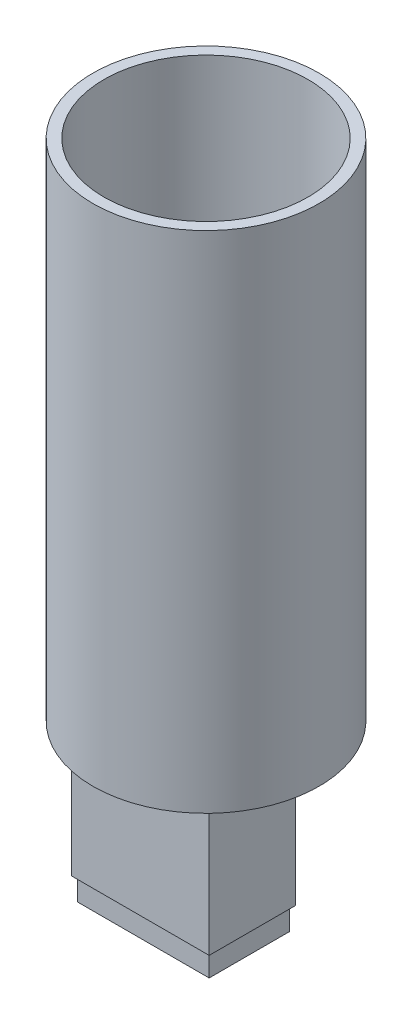
SolidWorks part; units mm, degrees
ref_plane "Front Plane" through (0, 0, 0) normal (0, 0, 1) x (1, 0, 0)
ref_plane "Top Plane" through (0, 0, 0) normal (0, 1, 0) x (1, 0, 0)
ref_plane "Right Plane" through (0, 0, 0) normal (1, 0, 0) x (0, 0, -1)
sketch "Sketch1" plane through (0, 0, 0) normal (0, 1, 0) x (1, 0, 0)
  circle A1 centre (0, 0) radius 15.01
  dimension "D2" = 30.02
extrude "Boss-Extrude1" add sketch "Sketch1" along normal blind 67 contours A1
sketch "Sketch2" plane through (0, 67, 0) normal (0, 1, 0) x (1, 0, 0)
  circle A0 centre (0, 0) radius 13.54
  dimension "D1" = 27.08
extrude "Cut-Extrude1" cut sketch "Sketch2" against normal blind 65
sketch "Sketch3" plane through (0, 0, 0) normal (0, -1, 0) x (1, 0, 0)
  line L1 (-9.15, 8.73) -> (9.15, 8.73)
  line L2 (-9.15, 8.73) -> (-9.15, -2.71)
  line L3 (-9.15, -2.71) -> (9.15, -2.71)
  line L4 (9.15, 8.73) -> (9.15, -2.71)
  line L5 (-9.15, 8.73) -> (9.15, -2.71) construction
  line L6 (-9.15, -2.71) -> (9.15, 8.73) construction
  circle A0 centre (0, 0) radius 15.01 construction
  point P0 (0, 3.01)
  dimension "D1" = 11.44
  dimension "D2" = 18.3
  dimension "D3" = 3.01
extrude "Boss-Extrude2" add sketch "Sketch3" along normal blind 18
ref_plane "Plane1" through (0, 0, 0) normal (0, -1, 0) x (-1, 0, 0)
sketch "Sketch4" plane through (0, 0, 0) normal (0, -1, 0) x (-1, 0, 0)
  line L0 (9.15, 2.71) -> (-9.15, 2.71) construction
  line L1 (-7.65, 1.21) -> (7.65, 1.21)
  line L2 (-7.65, 1.21) -> (-7.65, -7.23)
  line L3 (-7.65, -7.23) -> (7.65, -7.23)
  line L4 (7.65, 1.21) -> (7.65, -7.23)
  line L5 (-7.65, 1.21) -> (7.65, -7.23) construction
  line L6 (-7.65, -7.23) -> (7.65, 1.21) construction
  line L7 (-9.15, 2.71) -> (-9.15, -8.73) construction
  line L8 (-9.15, -8.73) -> (9.15, -8.73) construction
  line L9 (9.15, -8.73) -> (9.15, 2.71) construction
  point P0 (0, -3.01)
  point P11 (0, -8.73)
  point P14 (9.15, -3.01)
  dimension "D1" = 1.5
  dimension "D2" = 1.5
extrude "Cut-Extrude2" cut sketch "Sketch4" against normal blind 201 and the other way blind 16
sketch "Sketch5" plane through (0, -18, 0) normal (0, -1, 0) x (1, 0, 0)
  line L0 (-3.5, 3.01) -> (3.5, 3.01) construction
  line L1 (-3.5, 7.01) -> (3.5, 7.01)
  line L2 (-3.5, -0.99) -> (3.5, -0.99)
  line L3 (9.15, 8.73) -> (-9.15, 8.73) construction
  line L4 (9.15, -2.71) -> (9.15, 8.73) construction
  arc A0 (-3.5, 7.01) -> (-3.5, -0.99) centre (-3.5, 3.01) ccw
  arc A1 (3.5, -0.99) -> (3.5, 7.01) centre (3.5, 3.01) ccw
  point P2 (0, 3.01)
  point P10 (0, 8.73)
  point P13 (9.15, 3.01)
  dimension "D1" = 4
  dimension "D2" = 7
extrude "Cut-Extrude3" cut sketch "Sketch5" against normal blind 20
sketch "Sketch6" plane through (0, -18, 0) normal (0, -1, 0) x (1, 0, 0)
  line L0 (-3.5, 3.01) -> (3.5, 3.01) construction
  line L1 (-8.75, 8.33) -> (8.75, 8.33)
  line L2 (-8.75, 8.33) -> (-8.75, -2.31)
  line L3 (-8.75, -2.31) -> (8.75, -2.31)
  line L4 (8.75, 8.33) -> (8.75, -2.31)
  line L5 (-8.75, 8.33) -> (8.75, -2.31) construction
  line L6 (-8.75, -2.31) -> (8.75, 8.33) construction
  line L7 (-3.5, 7.01) -> (3.5, 7.01)
  line L8 (-3.5, -0.99) -> (3.5, -0.99)
  line L9 (3.5, 7.01) -> (-3.5, 7.01) construction
  line L10 (9.15, -2.71) -> (9.15, 8.73) construction
  line L11 (-3.5, -0.99) -> (3.5, -0.99) construction
  line L12 (9.15, 8.73) -> (-9.15, 8.73) construction
  line L13 (-9.15, 8.73) -> (-9.15, -2.71) construction
  arc A0 (-3.5, 7.01) -> (-3.5, -0.99) centre (-3.5, 3.01) ccw
  arc A1 (3.5, -0.99) -> (3.5, 7.01) centre (3.5, 3.01) ccw
  arc A2 (-3.5, 7.01) -> (-3.5, -0.99) centre (-3.5, 3.01) ccw construction
  point P0 (0, 3.01)
  point P7 (0, 3.01)
  point P17 (0, 0)
  point P21 (9.15, 3.01)
  point P22 (-3.5, -0.99)
  dimension "D1" = 0.4
  dimension "D2" = 0.4
extrude "Boss-Extrude3" add sketch "Sketch6" along normal blind 3
